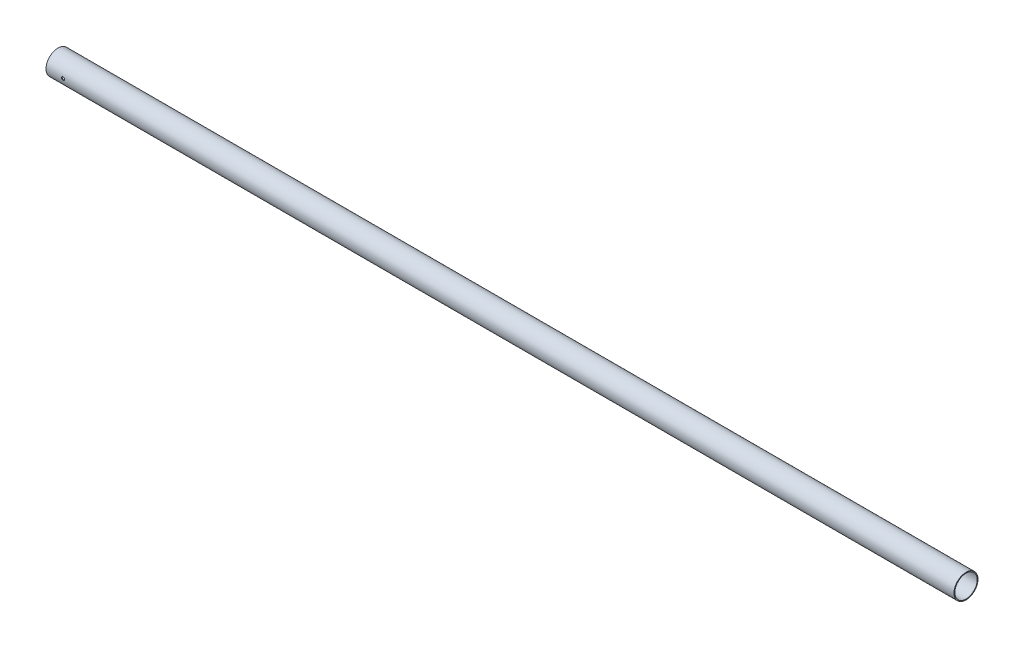
SolidWorks part; units mm, degrees
ref_plane "Front Plane" through (0, 0, 0) normal (0, 0, 1) x (1, 0, 0)
ref_plane "Top Plane" through (0, 0, 0) normal (0, 1, 0) x (1, 0, 0)
ref_plane "Right Plane" through (0, 0, 0) normal (1, 0, 0) x (0, 0, -1)
sketch "Sketch1" plane through (0, 0, 0) normal (1, 0, 0) x (0, 0, -1)
  circle A0 centre (0, 0) radius 12.7
  circle A1 centre (0, 0) radius 11.811
extrude "Boss-Extrude1" add sketch "Sketch1" along normal blind 960.836
sketch "Sketch2" plane through (0, 0, 0) normal (0, 0, 1) x (1, 0, 0)
  circle A0 centre (18, 0) radius 1.7
extrude "Cut-Extrude1" cut sketch "Sketch2" against normal through all and the other way through all
